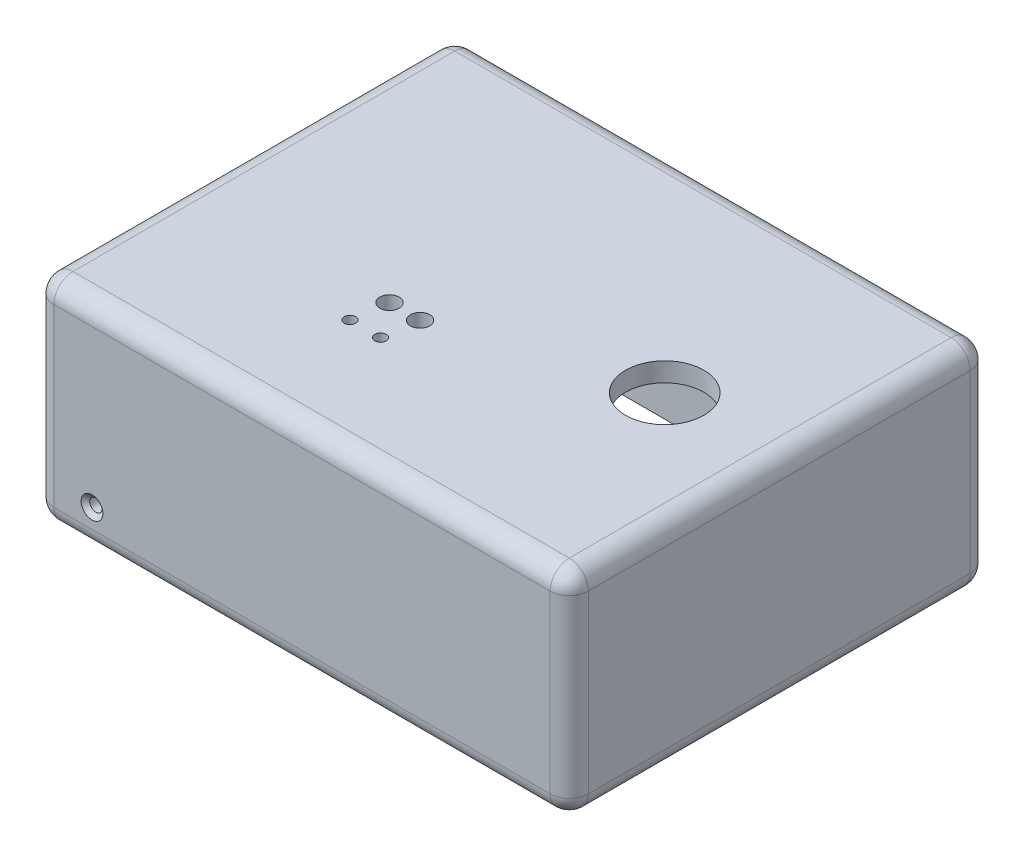
SolidWorks part; units mm, degrees
ref_plane "Front Plane" through (0, 0, 0) normal (0, 0, 1) x (1, 0, 0)
ref_plane "Top Plane" through (0, 0, 0) normal (0, 1, 0) x (1, 0, 0)
ref_plane "Right Plane" through (0, 0, 0) normal (1, 0, 0) x (0, 0, -1)
sketch "Sketch1" plane through (0, 0, 0) normal (0, 1, 0) x (1, 0, 0)
  line L1 (-70, -55) -> (70, -55)
  line L2 (-70, -55) -> (-70, 55)
  line L3 (-70, 55) -> (70, 55)
  line L4 (70, -55) -> (70, 55)
  line L5 (-70, -55) -> (70, 55) construction
  line L6 (-70, 55) -> (70, -55) construction
  point P0 (0, 0)
  dimension "D1" = 140
  dimension "D2" = 110
extrude "Boss-Extrude1" add sketch "Sketch1" along normal blind 56
sketch "Sketch2" plane through (0, 0, 0) normal (0, -1, 0) x (1, 0, 0)
  line L0 (-70, -55) -> (-70, 55) construction
  line L1 (-65, -50) -> (65, -50)
  line L2 (-65, -50) -> (-65, 50)
  line L3 (-65, 50) -> (65, 50)
  line L4 (65, -50) -> (65, 50)
  line L5 (-65, -50) -> (65, 50) construction
  line L6 (-65, 50) -> (65, -50) construction
  line L7 (-70, 55) -> (70, 55) construction
  point P0 (0, 0)
  dimension "D1" = 5
  dimension "D2" = 5
extrude "Cut-Extrude1" cut sketch "Sketch2" against normal blind 51
fillet "Fillet1" radius 5 4 edges at (0, 56, -55) (70, 56, 0) (0, 56, 55) (-70, 56, 0)
fillet "Fillet2" radius 5 8 edges at (-70, 25.5, -55) (70, 25.5, -55) (70, 25.5, 55) (-70, 25.5, 55) (-68.5355, 54.5355, -53.5355) (68.5355, 54.5355, -53.5355) (68.5355, 54.5355, 53.5355) (-68.5355, 54.5355, 53.5355)
fillet "Fillet3" radius 5 4 edges at (65, 51, 0) (0, 51, -50) (-65, 51, 0) (0, 51, 50)
fillet "Fillet4" radius 5 8 edges at (65, 23, 50) (65, 23, -50) (-65, 23, -50) (-65, 23, 50) (63.5355, 49.5355, 48.5355) (63.5355, 49.5355, -48.5355) (-63.5355, 49.5355, -48.5355) (-63.5355, 49.5355, 48.5355)
fillet "Fillet6" radius 5 8 edges at (-68.5355, 0, 53.5355) (-70, 0, 0) (-68.5355, 0, -53.5355) (0, 0, -55) (68.5355, 0, -53.5355) (70, 0, 0) (68.5355, 0, 53.5355) (0, 0, 55)
sketch "Sketch3" plane through (0, 56, 0) normal (0, 1, 0) x (1, 0, 0)
  line L0 (-70, -50) -> (-70, 50) construction
  line L1 (65, -55) -> (-65, -55) construction
  circle A0 centre (-16.48, -15.61) radius 2.54
  circle A1 centre (-8.48, -15.61) radius 2.54
  dimension "D1" = 8
  dimension "D2" = 53.52
  dimension "D3" = 39.39
extrude "Cut-Extrude2" cut sketch "Sketch3" against normal blind 5
sketch "Sketch4" plane through (0, 56, 0) normal (0, 1, 0) x (1, 0, 0)
  line L3 (65, -50) -> (65, 50) construction
  line L4 (-65, -50) -> (65, -50) construction
  circle A0 centre (40, 0) radius 10.25
  point P4 (65, 0)
  dimension "D1" = 20.5
  dimension "D2" = 25
  dimension "D3" = 50
extrude "Cut-Extrude3" cut sketch "Sketch4" against normal blind 5
sketch "Sketch5" plane through (0, 56, 0) normal (0, 1, 0) x (1, 0, 0)
  line L0 (-70, -50) -> (-70, 50) construction
  line L1 (65, -55) -> (-65, -55) construction
  circle A0 centre (-17.725, -24.71) radius 1.5
  circle A1 centre (-9.725, -24.71) radius 1.5
  dimension "D1" = 52.275
  dimension "D2" = 8
  dimension "D3" = 30.29
  dimension "D4" = 30.29
extrude "Cut-Extrude4" cut sketch "Sketch5" against normal blind 5
hole_wizard "CSK for #4 Flat Head Machine Screw (100)2" positions "Sketch10" profile "Sketch11" countersink size "#4" standard "ANSI Inch"
sketch "Sketch10" plane through (58.9654, 7.3812, 55) normal (0, 0, 1) x (1, 0, 0)
  point P0 (-113.9654, 2.6188)
  point P7 (-113.9654, 5.5688)
sketch "Sketch11" plane through (-55, 10, 55) normal (1, 0, 0) x (0, -1, 0)
  line L0 (0, 0) -> (0, 10.9806)
  line L1 (0, 10.9806) -> (1.6319, 10)
  line L2 (1.6319, 10) -> (1.6319, 1.0284)
  line L3 (1.6319, 1.0284) -> (2.8575, 0)
  line L4 (2.8575, 0) -> (0, 0)
  line L5 (-1.6319, 1.0284) -> (-2.8575, 0) construction
  line L6 (0, 10.9806) -> (-1.6319, 10) construction
  line L7 (0, -6.35) -> (0, 107.95) construction
  dimension "Hole Dia." = 3.2639
  dimension "Hole Depth" = 10
  dimension "Near C'Sink Dia." = 5.715
  dimension "Near C'Sink Angle" = 100
  dimension "Drill Angle" = 118
hole_wizard "CSK for #4 Flat Head Machine Screw (100)3" positions "Sketch12" profile "Sketch13" countersink size "#4" standard "ANSI Inch"
sketch "Sketch12" plane through (58.9654, 7.3812, -55) normal (0, 0, -1) x (-1, 0, 0)
  point P0 (3.9654, 2.6188)
  point P9 (-1.0346, 6.8662)
sketch "Sketch13" plane through (55, 10, -55) normal (1, 0, 0) x (0, 1, 0)
  line L0 (0, 0) -> (0, 10.9806)
  line L1 (0, 10.9806) -> (1.6319, 10)
  line L2 (1.6319, 10) -> (1.6319, 1.0284)
  line L3 (1.6319, 1.0284) -> (2.8575, 0)
  line L4 (2.8575, 0) -> (0, 0)
  line L5 (-1.6319, 1.0284) -> (-2.8575, 0) construction
  line L6 (0, 10.9806) -> (-1.6319, 10) construction
  line L7 (0, -6.35) -> (0, 107.95) construction
  dimension "Hole Dia." = 3.2639
  dimension "Hole Depth" = 10
  dimension "Near C'Sink Dia." = 5.715
  dimension "Near C'Sink Angle" = 100
  dimension "Drill Angle" = 118
